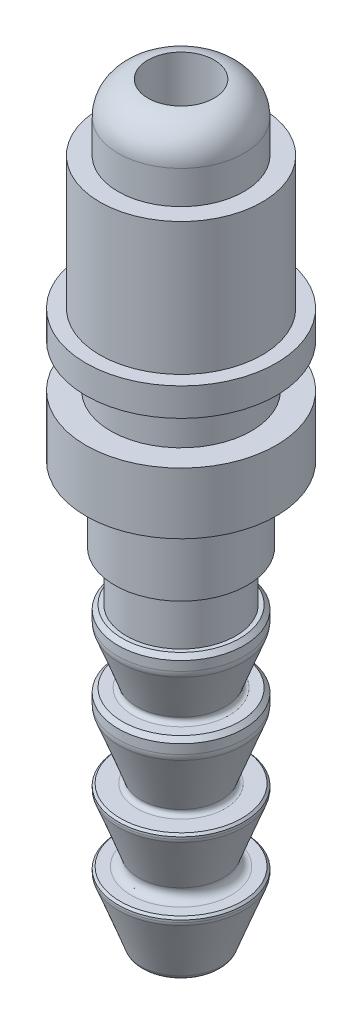
SolidWorks part; units mm, degrees
ref_plane "Front Plane" through (0, 0, 0) normal (0, 0, 1) x (1, 0, 0)
ref_plane "Top Plane" through (0, 0, 0) normal (0, 1, 0) x (1, 0, 0)
ref_plane "Right Plane" through (0, 0, 0) normal (1, 0, 0) x (0, 0, -1)
sketch "Sketch1" plane through (0, 0, 0) normal (0, 1, 0) x (1, 0, 0)
  circle A0 centre (0, 0) radius 5.75
  dimension "D1" = 11.5
extrude "Boss-Extrude1" add sketch "Sketch1" along normal blind 16
sketch "Sketch2" plane through (0, 16, 0) normal (0, 1, 0) x (1, 0, 0)
  circle A0 centre (0, 0) radius 4.9
  dimension "D1" = 9.8
extrude "Cut-Extrude1" cut sketch "Sketch2" against normal blind 8 flip side to cut
sketch "Sketch3" plane through (0, 16, 0) normal (0, 1, 0) x (1, 0, 0)
  circle A0 centre (0, 0) radius 3.8
  dimension "D1" = 7.6
extrude "Boss-Extrude2" add sketch "Sketch3" along normal blind 4
fillet "Fillet2" radius 2 1 edges at (0, 20, 3.8)
sketch "Sketch4" plane through (0, 0, 0) normal (0, -1, 0) x (1, 0, 0)
  circle A0 centre (0, 0) radius 4
  dimension "D1" = 8
extrude "Boss-Extrude3" add sketch "Sketch4" along normal blind 4.5
sketch "Sketch5" plane through (0, -4.5, 0) normal (0, -1, 0) x (1, 0, 0)
  circle A0 centre (0, 0) radius 3.3
  dimension "D1" = 6.6
extrude "Boss-Extrude4" add sketch "Sketch5" along normal blind 3
sketch "Sketch6" plane through (0, -7.5, 0) normal (0, -1, 0) x (1, 0, 0)
  circle A0 centre (0, 0) radius 3.8
  dimension "D1" = 7.6
extrude "Boss-Extrude5" add sketch "Sketch6" along normal blind 1
ref_plane "Plane1" through (0, -12.5, 0) normal (0, -1, 0) x (-1, 0, 0)
sketch "Sketch7" plane through (0, -12.5, 0) normal (0, -1, 0) x (-1, 0, 0)
  circle A0 centre (0, 0) radius 3.05
  dimension "D1" = 6.1
ref_axis "Axis1" through (0, 8, 0) along (0, -1, 0)
sketch "Sketch10" plane through (0, -12.5, 0) normal (0, -1, 0) x (-1, 0, 0)
  circle A0 centre (0, 0) radius 3.8 construction
  circle A1 centre (0, 0) radius 3.8
extrude "Boss-Extrude6" add sketch "Sketch10" against normal up to next
sketch "Sketch11" plane through (0, 0, 0) normal (0, 0, 1) x (1, 0, 0)
  line L0 (-2.3, -12.5) -> (-3.8, -8.5)
  line L1 (-3.05, -12.5) -> (3.05, -12.5) construction
  line L2 (-55, -12.5) -> (55, -12.5) construction
  line L3 (-3.8, -7.5) -> (-3.8, -12.5) construction
  line L4 (-3.8, -8.5) -> (-3.8, -12.5)
  line L5 (-3.8, -12.5) -> (-2.3, -12.5)
  line L6 (3.8, -7.5) -> (-3.8, -7.5) construction
  dimension "D1" = 1
  dimension "D2" = 1.5
revolve "Cut-Revolve1" cut sketch "Sketch11" angle 360 about axis through (0, 8, 0) along (0, -1, 0)
pattern_linear "LPattern1" count 4 spacing 4.35 along (0, -1, 0) of "Cut-Revolve1", "Boss-Extrude6", "Boss-Extrude5"
chamfer "Chamfer1" distance 0.25 angle 45 1 edges at (0, -7.5, -3.8)
chamfer "Chamfer2" distance 0.25 angle 45 1 edges at (0, -11.85, -3.8)
chamfer "Chamfer3" distance 0.125 angle 45 1 edges at (0, -16.85, 3.8)
chamfer "Chamfer4" distance 0.125 angle 45 1 edges at (0, -21.2, 3.8)
fillet "Fillet3" radius 0.5 2 edges at (0, -17.2, 3.8) (0, -21.55, 3.8)
fillet "Fillet4" radius 1 2 edges at (0, -12.85, 3.8) (0, -8.5, 3.8)
fillet "Fillet5" radius 0.25 2 edges at (0, -16.85, 2.3) (0, -11.85, -2.5437)
fillet "Fillet6" radius 0.5 1 edges at (0, -21.2, 2.3)
fillet "Fillet7" radius 0.5 1 edges at (0, -25.55, 2.3)
sketch "Sketch12" plane through (0, 0, 0) normal (1, 0, 0) x (0, 0, -1)
  line L0 (-5.75, 6.3) -> (-4.25, 6.3)
  line L1 (-5.75, 8) -> (-5.75, 0) construction
  line L2 (-4.25, 6.3) -> (-4.25, 3.7)
  line L3 (-4.25, 3.7) -> (-5.75, 3.7)
  line L4 (-5.75, 8) -> (-5.75, 0) construction
  line L5 (-5.75, 3.7) -> (-5.75, 6.3)
  line L6 (5.75, 8) -> (-5.75, 8) construction
  dimension "D1" = 2.6
  dimension "D2" = 1.7
  dimension "D3" = 1.5
revolve "Cut-Revolve2" cut sketch "Sketch12" angle 360 about axis through (0, 8, 0) along (0, -1, 0)
sketch "Sketch13" plane through (0, -25.55, 0) normal (0, -1, 0) x (1, 0, 0)
  circle A0 centre (0, 0) radius 2
  dimension "D1" = 4
extrude "Cut-Extrude2" cut sketch "Sketch13" against normal through all
